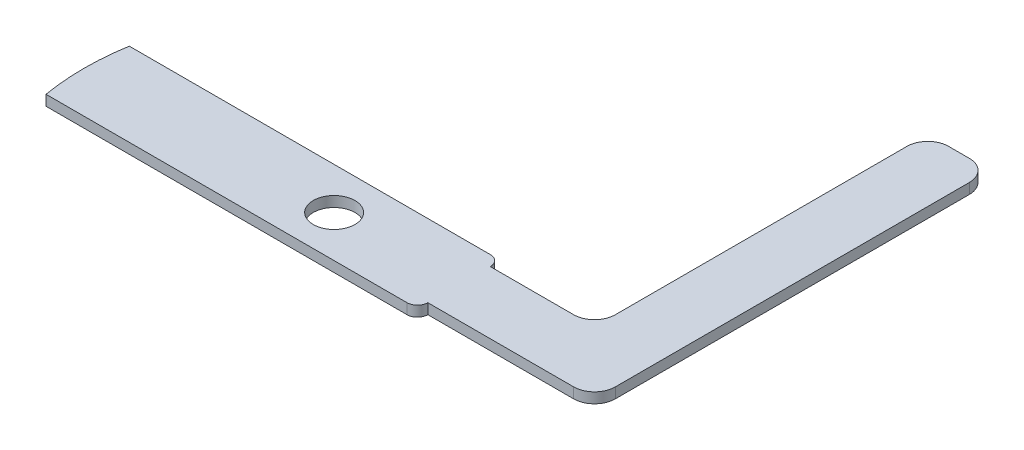
SolidWorks part; units mm, degrees
ref_plane "Front Plane" through (0, 0, 0) normal (0, 0, 1) x (1, 0, 0)
ref_plane "Top Plane" through (0, 0, 0) normal (0, 1, 0) x (1, 0, 0)
ref_plane "Right Plane" through (0, 0, 0) normal (1, 0, 0) x (0, 0, -1)
sketch "Sketch1" plane through (0, 0, 0) normal (0, 1, 0) x (1, 0, 0)
  line L0 (0, 6.35) -> (-44.45, 6.35) construction
  line L1 (0, 0) -> (-44.45, 0)
  line L2 (0, 0) -> (0, 12.7)
  line L3 (0, 12.7) -> (-44.45, 12.7)
  line L4 (-44.45, 0) -> (-44.45, 12.7) construction
  line L5 (0, 12.7) -> (12.7, 12.7)
  line L6 (12.7, 12.7) -> (12.7, 11.1125)
  line L7 (12.7, 11.1125) -> (28.575, 11.1125)
  line L8 (38.1, 11.1125) -> (38.1, 1.5875)
  line L9 (38.1, 1.5875) -> (12.7, 1.5875)
  line L10 (12.7, 1.5875) -> (12.7, 0)
  line L11 (12.7, 0) -> (0, 0)
  line L12 (38.1, 11.1125) -> (38.1, 61.9125)
  line L13 (38.1, 61.9125) -> (28.575, 61.9125)
  line L14 (28.575, 61.9125) -> (28.575, 11.1125)
  line L15 (28.575, 11.1125) -> (38.1, 11.1125) construction
  circle A0 centre (-6.35, 6.35) radius 3.175
  arc A1 (-43.9171, 12.7) -> (-43.9171, 0) centre (-6.35, 6.35) ccw
  dimension "D4" = 6.35
  dimension "D1" = 12.7
  dimension "D2" = 44.45
  dimension "D3" = 6.35
  dimension "D5" = 12.7
  dimension "D6" = 25.4
  dimension "D7" = 9.525
  dimension "D8" = 50.8
extrude "Boss-Extrude1" add sketch "Sketch1" along normal blind 1.5875 contours L2 L0 A0 L4 L1 | L0 L2 L3 L4 A0 | L11 L10 L9 L8 L6 L5 L2 region at (-23.079, 0, -6.35) region at (0.727, 0, -6.35)
fillet "Fillet1" radius 3.175 4 edges at (38.1, 0.7937, -61.9125) (28.575, 0.7937, -61.9125) (28.575, 0.7937, -11.1125) (38.1, 0.7937, -1.5875)
fillet "Fillet2" radius 1.5875 2 edges at (12.7, 0.7937, 0) (12.7, 0.7937, -12.7)
